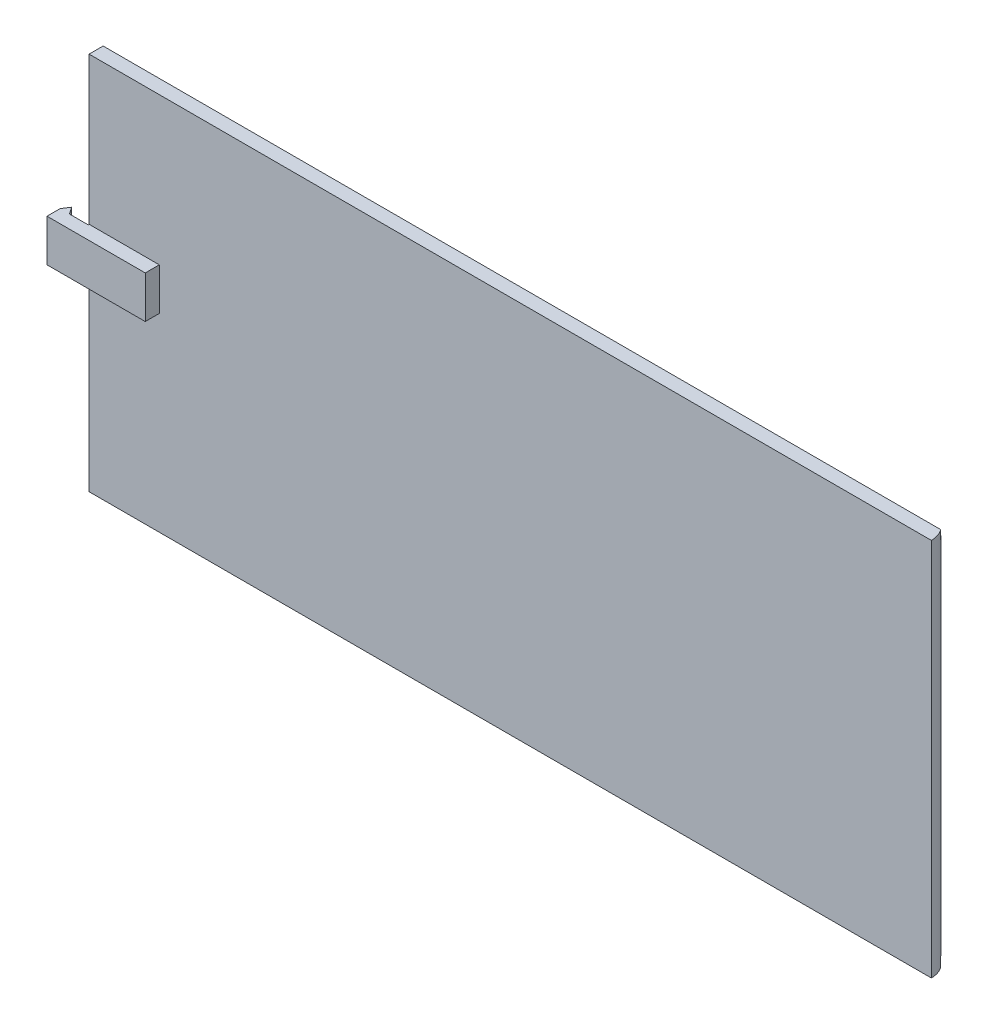
SolidWorks part; units mm, degrees
ref_plane "Front Plane" through (0, 0, 0) normal (0, 0, 1) x (1, 0, 0)
ref_plane "Top Plane" through (0, 0, 0) normal (0, 1, 0) x (1, 0, 0)
ref_plane "Right Plane" through (0, 0, 0) normal (1, 0, 0) x (0, 0, -1)
sketch "Sketch1" plane through (0, 0, 0) normal (0, 0, 1) x (1, 0, 0)
  line L1 (-90, -40.5) -> (90, -40.5)
  line L2 (-90, -40.5) -> (-90, 40.5)
  line L3 (-90, 40.5) -> (90, 40.5)
  line L4 (90, -40.5) -> (90, 40.5)
  line L5 (-90, -40.5) -> (90, 40.5) construction
  line L6 (-90, 40.5) -> (90, -40.5) construction
  point P0 (0, 0)
  dimension "D1" = 180
  dimension "D2" = 81
extrude "Boss-Extrude1" add sketch "Sketch1" along normal blind 5
fillet "Fillet1" radius 5 1 edges at (90, 0, 0)
sketch "Sketch2" plane through (-90, 0, 0) normal (-1, 0, 0) x (0, 0, 1)
  line L1 (0, 40.5) -> (2, 40.5)
  line L2 (0, 40.5) -> (0, 38.5)
  line L3 (0, 38.5) -> (2, 38.5)
  line L4 (2, 40.5) -> (2, 38.5)
  line L5 (0, -40.5) -> (2, -40.5)
  line L6 (0, -40.5) -> (0, -38.5)
  line L7 (0, -38.5) -> (2, -38.5)
  line L8 (2, -40.5) -> (2, -38.5)
  point P10 (0, 39.5)
  dimension "D1" = 2
  dimension "D2" = 2
  dimension "D3" = 2
  dimension "D4" = 2
extrude "Cut-Extrude1" cut sketch "Sketch2" against normal through all
sketch "Sketch3" plane through (0, 0, 5) normal (0, 0, 1) x (1, 0, 0)
  line L0 (-90, 40.5) -> (-90, -40.5) construction
  line L1 (-90, 0) -> (-75, 0)
  line L2 (-90, 0) -> (-90, 9)
  line L3 (-90, 9) -> (-75, 9)
  line L4 (-75, 0) -> (-75, 9)
  dimension "D1" = 9
  dimension "D2" = 15
extrude "Boss-Extrude2" add sketch "Sketch3" along normal blind 3
sketch "Sketch4" plane through (-90, 0, 0) normal (-1, 0, 0) x (0, 0, 1)
  line L0 (8, 0) -> (5, 0) construction
  line L1 (8, 9) -> (5.2, 9)
  line L2 (8, 9) -> (8, 0)
  line L3 (8, 0) -> (5.2, 0)
  line L4 (5.2, 9) -> (5.2, 0)
  dimension "D1" = 2.8
extrude "Boss-Extrude3" add sketch "Sketch4" along normal blind 6
sketch "Sketch5" plane through (0, 9, 0) normal (0, 1, 0) x (1, 0, 0)
  line L0 (-96, -5.2) -> (-95.031, -3.7)
  line L1 (-95.031, -3.7) -> (-94, -5.2)
  line L2 (-96, -5.2) -> (-90, -5.2) construction
  line L3 (-94, -5.2) -> (-96, -5.2)
  dimension "D1" = 2
  dimension "D2" = 1.5
extrude "Boss-Extrude4" add sketch "Sketch5" against normal up to surface (9 mm away) up to face at (-87, 0, 6.0667)
